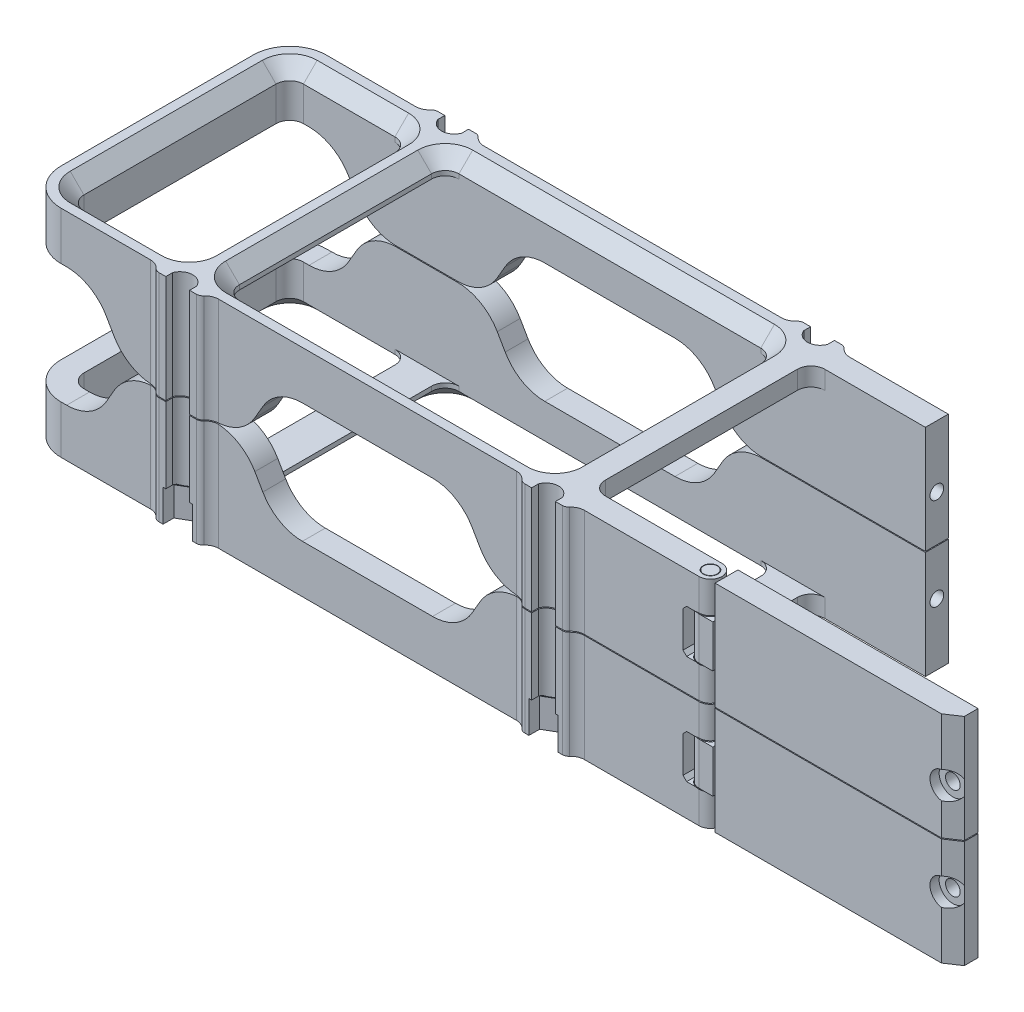
SolidWorks part; units mm, degrees
ref_plane "Płaszczyzna przednia" through (0, 0, 0) normal (0, 0, 1) x (1, 0, 0)
ref_plane "Płaszczyzna górna" through (0, 0, 0) normal (0, 1, 0) x (1, 0, 0)
ref_plane "Płaszczyzna prawa" through (0, 0, 0) normal (1, 0, 0) x (0, 0, -1)
sketch "Szkic1" plane through (0, 0, 0) normal (0, 1, 0) x (1, 0, 0)
  line L0 (-70, -24) -> (75, -24)
  line L1 (75, -24) -> (75, -29)
  line L3 (-75, -29) -> (-75, -24)
  line L4 (75, -29) -> (45.6, -29)
  line L5 (0, 29) -> (0, -29) construction
  line L6 (-34.4, -29) -> (34.4, -29)
  line L7 (-75, -29) -> (-45.6, -29)
  line L8 (-45.6, -29) -> (-40, -29) construction
  line L9 (-40, -29) -> (-34.4, -29) construction
  line L10 (34.4, -29) -> (40, -29) construction
  line L11 (45.6, -29) -> (40, -29) construction
  line L12 (-55, 0) -> (55, 0) construction
  line L13 (45.6, 29) -> (40, 29) construction
  line L14 (34.4, 29) -> (40, 29) construction
  line L15 (-40, 29) -> (-34.4, 29) construction
  line L16 (-45.6, 29) -> (-40, 29) construction
  line L17 (-75, 29) -> (-45.6, 29)
  line L18 (-34.4, 29) -> (34.4, 29)
  line L19 (69, 29) -> (45.6, 29)
  line L20 (-75, 29) -> (-75, 24)
  line L21 (75, 24) -> (75, 29) construction
  line L22 (-70, 24) -> (69, 24)
  line L23 (-75, 24) -> (-75, -24)
  line L24 (-70, 24) -> (-70, -24)
  line L25 (-75, 24) -> (-70, 24) construction
  line L26 (-75, -24) -> (-70, -24) construction
  line L27 (69, 29) -> (69, 24)
  line L28 (69, 24) -> (75, 24) construction
  line L29 (75, 29) -> (69, 29) construction
  arc A0 (-45.6, -29) -> (-34.4, -29) centre (-40, -29) ccw
  arc A1 (34.4, -29) -> (45.6, -29) centre (40, -29) ccw
  arc A2 (-34.4, -29) -> (-45.6, -29) centre (-40, -29) ccw construction
  arc A3 (45.6, -29) -> (34.4, -29) centre (40, -29) ccw construction
  arc A4 (45.6, 29) -> (34.4, 29) centre (40, 29) cw construction
  arc A5 (-34.4, 29) -> (-45.6, 29) centre (-40, 29) cw construction
  arc A6 (34.4, 29) -> (45.6, 29) centre (40, 29) cw
  arc A7 (-45.6, 29) -> (-34.4, 29) centre (-40, 29) cw
  point P4 (0, 0)
  point P12 (0, 0)
  point P16 (0, -29)
  point P31 (0, 29)
  dimension "D1" = 11.2
  dimension "D2" = 11.2
  dimension "D3" = 80
  dimension "D4" = 150
  dimension "D6" = 58
  dimension "D7" = 5
  dimension "D5" = 48
  dimension "D8" = 6
extrude "Dodanie-wyciągnięcie1" add sketch "Szkic1" along normal blind 23.5 separate body
sketch "Szkic2" plane through (0, 23.5, 0) normal (0, 1, 0) x (1, 0, 0)
  line L0 (-45.6, -29) -> (-42.6, -29) construction
  line L3 (-37.4, -29) -> (-34.4, -29) construction
  line L4 (-44.1, -30.5) -> (-42.6, -30.5)
  line L5 (-42.6, -29) -> (-42.6, -30.5)
  line L6 (-37.4, -29) -> (-37.4, -30.5)
  line L7 (-42.6, -30.5) -> (-42.1237, -30.5) construction
  line L8 (-42.1237, -30.5) -> (-37.8763, -30.5) construction
  line L9 (-37.8763, -30.5) -> (-37.4, -30.5) construction
  line L10 (-37.4, -30.5) -> (-35.9, -30.5)
  line L12 (-12.925, 0) -> (12.925, 0) construction
  line L13 (-37.8763, 30.5) -> (-37.4, 30.5) construction
  line L14 (-42.1237, 30.5) -> (-37.8763, 30.5) construction
  line L15 (-42.6, 30.5) -> (-42.1237, 30.5) construction
  line L16 (-37.4, 29) -> (-34.4, 29) construction
  line L22 (-45.6, 29) -> (-42.6, 29) construction
  line L23 (-37.4, 30.5) -> (-35.9, 30.5)
  line L24 (-37.4, 29) -> (-37.4, 30.5)
  line L25 (-42.6, 29) -> (-42.6, 30.5)
  line L26 (-44.1, 30.5) -> (-42.6, 30.5)
  line L27 (0, -12.925) -> (0, 12.925) construction
  line L28 (45.6, 29) -> (42.6, 29) construction
  line L29 (37.4, 29) -> (34.4, 29) construction
  line L30 (42.6, 30.5) -> (42.1237, 30.5) construction
  line L31 (42.1237, 30.5) -> (37.8763, 30.5) construction
  line L40 (37.8763, 30.5) -> (37.4, 30.5) construction
  line L41 (37.8763, -30.5) -> (37.4, -30.5) construction
  line L42 (42.1237, -30.5) -> (37.8763, -30.5) construction
  line L43 (42.6, -30.5) -> (42.1237, -30.5) construction
  line L44 (37.4, -29) -> (34.4, -29) construction
  line L45 (45.6, -29) -> (42.6, -29) construction
  line L46 (44.1, 30.5) -> (42.6, 30.5)
  line L47 (42.6, 29) -> (42.6, 30.5)
  line L48 (37.4, 29) -> (37.4, 30.5)
  line L49 (37.4, 30.5) -> (35.9, 30.5)
  line L50 (37.4, -30.5) -> (35.9, -30.5)
  line L51 (37.4, -29) -> (37.4, -30.5)
  line L52 (42.6, -29) -> (42.6, -30.5)
  line L53 (44.1, -30.5) -> (42.6, -30.5)
  arc A3 (-42.1237, -30.5) -> (-37.8763, -30.5) centre (-40, -29) ccw construction
  arc A4 (-45.6, -29) -> (-44.1, -30.5) centre (-44.1, -29) ccw
  arc A5 (-34.4, -29) -> (-35.9, -30.5) centre (-35.9, -29) cw
  arc A6 (-45.6, -29) -> (-34.4, -29) centre (-40, -29) ccw
  arc A7 (-42.6, -29) -> (-42.1237, -30.5) centre (-40, -29) ccw construction
  arc A8 (-37.8763, -30.5) -> (-37.4, -29) centre (-40, -29) ccw construction
  arc A10 (-37.8763, 30.5) -> (-37.4, 29) centre (-40, 29) cw construction
  arc A11 (-42.6, 29) -> (-42.1237, 30.5) centre (-40, 29) cw construction
  arc A12 (-42.1237, 30.5) -> (-37.8763, 30.5) centre (-40, 29) cw construction
  arc A17 (-42.6, 29) -> (-37.4, 29) centre (-40, 30) ccw
  arc A18 (-45.6, 29) -> (-34.4, 29) centre (-40, 29) cw
  arc A19 (-34.4, 29) -> (-35.9, 30.5) centre (-35.9, 29) ccw
  arc A20 (-45.6, 29) -> (-44.1, 30.5) centre (-44.1, 29) cw
  arc A21 (42.1237, 30.5) -> (37.8763, 30.5) centre (40, 29) ccw construction
  arc A22 (42.6, 29) -> (42.1237, 30.5) centre (40, 29) ccw construction
  arc A31 (-42.6, -29) -> (-37.4, -29) centre (-40, -30) cw
  arc A32 (37.8763, 30.5) -> (37.4, 29) centre (40, 29) ccw construction
  arc A33 (37.8763, -30.5) -> (37.4, -29) centre (40, -29) cw construction
  arc A34 (42.6, -29) -> (42.1237, -30.5) centre (40, -29) cw construction
  arc A35 (42.1237, -30.5) -> (37.8763, -30.5) centre (40, -29) cw construction
  arc A36 (42.6, -29) -> (37.4, -29) centre (40, -30) ccw
  arc A37 (45.6, 29) -> (44.1, 30.5) centre (44.1, 29) ccw
  arc A38 (34.4, 29) -> (35.9, 30.5) centre (35.9, 29) cw
  arc A39 (45.6, 29) -> (34.4, 29) centre (40, 29) ccw
  arc A40 (42.6, 29) -> (37.4, 29) centre (40, 30) cw
  arc A41 (45.6, -29) -> (34.4, -29) centre (40, -29) cw
  arc A42 (34.4, -29) -> (35.9, -30.5) centre (35.9, -29) ccw
  arc A43 (45.6, -29) -> (44.1, -30.5) centre (44.1, -29) cw
  dimension "D1" = 5.2
  dimension "D2" = 1
extrude "Wytnij-wyciągnięcie1" cut sketch "Szkic2" against normal through all
fillet "Zaokrąglenie1" radius 8 2 edges at (-75, 11.75, -29) (-75, 11.75, 29)
fillet "Zaokrąglenie2" radius 3 2 edges at (-70, 11.75, -24) (-70, 11.75, 24)
fillet "Zaokrąglenie3" radius 3 8 edges at (-34.4, 11.75, 29) (-45.6, 11.75, 29) (-45.6, 11.75, -29) (-34.4, 11.75, -29) (34.4, 11.75, -29) (45.6, 11.75, -29) (45.6, 11.75, 29) (34.4, 11.75, 29)
sketch "Szkic6" plane through (0, 23.5, 0) normal (0, 1, 0) x (1, 0, 0)
  line L0 (72.5, -26.5) -> (72.5, -24) construction
  line L1 (75, -24) -> (-67, -24) construction
  line L2 (72.5, -24) -> (75, -24) construction
  circle A0 centre (72.5, -26.5) radius 1.6
  dimension "D3" = 3.2
  dimension "D1" = 2.5
  dimension "D2" = 2.5
extrude "Wytnij-wyciągnięcie4" cut sketch "Szkic6" against normal through all
sketch "Szkic7" plane through (0, 0, 29) normal (0, 0, 1) x (1, 0, 0)
  line L0 (75, 0) -> (75, 7) construction
  line L1 (75, 23.5) -> (75, 0) construction
  line L2 (75, 7) -> (69, 7)
  line L3 (69, 7) -> (69, 16.5)
  line L4 (69, 16.5) -> (75, 16.5)
  line L5 (75, 16.5) -> (75, 7)
  dimension "D1" = 7
  dimension "D2" = 9.5
  dimension "D3" = 6
extrude "Wytnij-wyciągnięcie5" cut sketch "Szkic7" against normal through all
chamfer "Sfazowanie1" distance 1 angle 45 2 edges at (72.5, 16.5, 28.1) (72.5, 7, 24.9)
sketch "Szkic8" plane through (0, 0, 0) normal (0, -1, 0) x (1, 0, 0)
  circle A0 centre (72.5, 26.5) radius 1.5
  dimension "D1" = 3
extrude "Dodanie-wyciągnięcie2" add sketch "Szkic8" against normal blind 23.5 separate body
ref_plane "Płaszczyzna1" through (0, 7.1, 0) normal (0, 1, 0) x (1, 0, 0)
sketch "Szkic9" plane through (0, 7.1, 0) normal (0, 1, 0) x (1, 0, 0)
  circle A0 centre (72.5, -26.5) radius 2.5
  dimension "D1" = 5
extrude "Dodanie-wyciągnięcie3" add sketch "Szkic9" along normal blind 9.3
chamfer "Sfazowanie2" distance 1 angle 45 2 edges at (71, 7.1, 26.5) (71, 16.4, 26.5)
sketch "Szkic10" plane through (0, 0, 0) normal (0, 1, 0) x (1, 0, 0)
  line L0 (0, 0) -> (69.5, 0) construction
  line L1 (69.5, 0) -> (69.5, 29)
  line L2 (69.5, 29) -> (74.5, 29)
  line L3 (74.5, 29) -> (74.5, -23.5)
  line L4 (74.5, -23.5) -> (69.5, -23.5)
  line L5 (69.5, -23.5) -> (69.5, 0)
  dimension "D1" = 69.5
  dimension "D2" = 5
  dimension "D3" = 29
  dimension "D4" = 23.5
extrude "Dodanie-wyciągnięcie4" add sketch "Szkic10" along normal blind 23.5 separate body
sketch "Szkic12" plane through (0, 7.1, 0) normal (0, 1, 0) x (1, 0, 0)
  line L0 (75, -26.5) -> (75, -23.5)
  line L1 (69.5, -23.5) -> (74.5, -23.5) construction
  line L2 (70, -26.5) -> (70, -23.5)
  line L3 (70, -23.5) -> (75, -23.5)
  arc A0 (70, -26.5) -> (75, -26.5) centre (72.5, -26.5) ccw
  arc A1 (75, -26.5) -> (70, -26.5) centre (72.5, -26.5) ccw construction
  dimension "D1" = 5
extrude "Dodanie-wyciągnięcie5" add sketch "Szkic12" along normal blind 9.3
fillet "Zaokrąglenie4" radius 2.5 4 edges at (75, 3.5, 24) (75, 3.5, 29) (75, 20, 29) (75, 20, 24)
ref_axis "Oś1" through (72.5, 25.1302, 26.5) along (0, -1, 0)
sketch "Szkic13" plane through (74.5, 0, 0) normal (1, 0, 0) x (0, 0, -1)
  line L0 (29, 23.5) -> (29, 0) construction
  line L2 (-23.5, 23.5) -> (29, 23.5) construction
  circle A0 centre (26.5, 13.5) radius 1.6
  dimension "D2" = 10
  dimension "D3" = 3.2
  dimension "D1" = 2.5
extrude "Wytnij-wyciągnięcie6" cut sketch "Szkic13" against normal up to next (5 mm away)
sketch "Szkic14" plane through (69, 0, 0) normal (1, 0, 0) x (0, 0, -1)
  circle A0 centre (26.5, 13.5) radius 1.5
  dimension "D1" = 3
extrude "Wytnij-wyciągnięcie7" cut sketch "Szkic14" against normal blind 10
sketch "Szkic15" plane through (74.5, 0, 0) normal (1, 0, 0) x (0, 0, -1)
  circle A0 centre (26.5, 13.5) radius 3
  dimension "D1" = 6
chamfer "Sfazowanie3" distance 3 distance2 2 1 edges at (74.5, 11.75, -29) first distance on face at (74.5, 13.5, -28.1)
extrude "Wytnij-wyciągnięcie8" cut sketch "Szkic15" against normal blind 2
chamfer "Sfazowanie4" distance 0.8 angle 45 2 edges at (69, 16.5, 26.5) (69, 7, 26.5)
move or copy body "Obiekt-Przenieś/Kopiuj1" bodies to move or copy 114 copy no rotation origin (72.5, 0, 26.5) rotation axis (0, -1, 0) rotation angle 90
sketch "Szkic16" plane through (0, 0, 0) normal (0, -1, 0) x (1, 0, 0)
  line L0 (-40, 0) -> (40, 0) construction
  line L1 (40, 24) -> (40, -24) construction
  line L2 (-67, -24) -> (69, -24) construction
  line L4 (72.5, 24) -> (-67, 24) construction
  line L5 (44, 24) -> (44, -24)
  line L6 (44, -24) -> (40, -24)
  line L7 (36, 24) -> (44, 24)
  line L8 (36, 24) -> (36, -24)
  line L9 (36, -24) -> (40, -24)
  line L10 (0, -12.925) -> (0, 12.925) construction
  line L11 (-44, -24) -> (-40, -24)
  line L12 (-36, -24) -> (-40, -24)
  line L13 (-44, 24) -> (-44, -24)
  line L14 (-36, 24) -> (-44, 24)
  line L15 (-36, 24) -> (-36, -24)
  point P4 (0, 0)
  point P10 (40, 0)
  point P17 (40, 24)
  dimension "D1" = 80
  dimension "D2" = 8
extrude "Dodanie-wyciągnięcie6" add sketch "Szkic16" against normal blind 4
sketch "Szkic17" plane through (0, 0, 29) normal (0, 0, 1) x (1, 0, 0)
  line L0 (-75, 10.5) -> (-60, 10.5)
  line L1 (-75, 0) -> (-75, 23.5) construction
  line L2 (-60, 10.5) -> (-52.4944, 23.5)
  line L3 (-67, 23.5) -> (-47.4541, 23.5) construction
  line L4 (-52.4944, 23.5) -> (-75, 23.5)
  line L5 (-75, 23.5) -> (-75, 10.5)
  dimension "D1" = 15
  dimension "D2" = 60
  dimension "D3" = 13
extrude "Wytnij-wyciągnięcie9" cut sketch "Szkic17" against normal through all
sketch "Szkic18" plane through (0, 0, 29) normal (0, 0, 1) x (1, 0, 0)
  line L0 (-27.5056, 23.5) -> (-20, 10.5)
  line L1 (-32.5459, 23.5) -> (32.5459, 23.5) construction
  line L2 (0, 0) -> (0, 10.5) construction
  line L3 (-32.5459, 0) -> (32.5459, 0) construction
  line L4 (20, 10.5) -> (-20, 10.5)
  line L5 (20, 10.5) -> (27.5056, 23.5)
  line L6 (27.5056, 23.5) -> (-27.5056, 23.5)
  point P11 (0, 10.5)
  dimension "D1" = 60
  dimension "D2" = 60
  dimension "D3" = 40
  dimension "D4" = 13
extrude "Wytnij-wyciągnięcie10" cut sketch "Szkic18" against normal through all
fillet "Zaokrąglenie5" radius 10 12 edges at (-52.4944, 23.5, -26.5) (-52.4944, 23.5, 26.5) (-27.5056, 23.5, 26.5) (-20, 10.5, 26.5) (20, 10.5, 26.5) (27.5056, 23.5, 26.5) (-27.5056, 23.5, -26.5) (-20, 10.5, -26.5) (20, 10.5, -26.5) (27.5056, 23.5, -26.5) (-60, 10.5, -26.5) (-60, 10.5, 26.5)
fillet "Zaokrąglenie6" radius 3 8 edges at (-44, 2, -24) (-44, 2, 24) (-36, 2, 24) (-36, 2, -24) (36, 2, -24) (44, 2, -24) (36, 2, 24) (44, 2, 24)
chamfer "Sfazowanie5" distance 3 angle 45 16 edges at (-44, 0, 0) (-44.8787, 0, 23.1213) (-44.8787, 0, -23.1213) (-57, 0, 24) (-57, 0, -24) (-69.1213, 0, 23.1213) (-69.1213, 0, -23.1213) (-70, 0, 0) (36, 0, 0) (35.1213, 0, -23.1213) (35.1213, 0, 23.1213) (0, 0, -24) (0, 0, 24) (-35.1213, 0, -23.1213) (-35.1213, 0, 23.1213) (-36, 0, 0)
ref_plane "Płaszczyzna2" through (0, 23.6, 0) normal (0, 1, 0) x (1, 0, 0)
mirror "Lustro1" about plane through (0, 23.6, 0) normal (0, 1, 0) of bodies 118 111
sketch "Szkic19" plane through (0, 0, 0) normal (0, -1, 0) x (1, 0, 0)
  line L1 (40, -26.305) -> (36.8, -28.1525)
  line L2 (36.8, -28.1525) -> (36.8, -31.8475)
  line L3 (36.8, -31.8475) -> (40, -33.695)
  line L4 (40, -33.695) -> (43.2, -31.8475)
  line L5 (43.2, -31.8475) -> (43.2, -28.1525)
  line L6 (43.2, -28.1525) -> (40, -26.305)
  line L7 (-40, -26.305) -> (-43.2, -28.1525)
  line L8 (-43.2, -28.1525) -> (-43.2, -31.8475)
  line L9 (-43.2, -31.8475) -> (-40, -33.695)
  line L10 (-40, -33.695) -> (-36.8, -31.8475)
  line L11 (-36.8, -31.8475) -> (-36.8, -28.1525)
  line L12 (-36.8, -28.1525) -> (-40, -26.305)
  line L13 (-40, 26.305) -> (-36.8, 28.1525)
  line L14 (-36.8, 28.1525) -> (-36.8, 31.8475)
  line L15 (-36.8, 31.8475) -> (-40, 33.695)
  line L16 (-40, 33.695) -> (-43.2, 31.8475)
  line L17 (-43.2, 31.8475) -> (-43.2, 28.1525)
  line L18 (-43.2, 28.1525) -> (-40, 26.305)
  line L19 (40, 26.305) -> (43.2, 28.1525)
  line L20 (43.2, 28.1525) -> (43.2, 31.8475)
  line L21 (43.2, 31.8475) -> (40, 33.695)
  line L22 (40, 33.695) -> (36.8, 31.8475)
  line L23 (36.8, 31.8475) -> (36.8, 28.1525)
  line L24 (36.8, 28.1525) -> (40, 26.305)
  circle A0 centre (40, -30) radius 3.2 construction
  circle A1 centre (-40, -30) radius 3.2 construction
  circle A2 centre (-40, 30) radius 3.2 construction
  circle A3 centre (40, 30) radius 3.2 construction
  dimension "D1" = 6.4
  dimension "D2" = 6.4
  dimension "D3" = 6.4
  dimension "D4" = 6.4
extrude "Wytnij-wyciągnięcie11" cut sketch "Szkic19" against normal blind 7
chamfer "Sfazowanie6" distance 0.7 angle 45 8 edges at (-38.4, 7, 27.2287) (-41.6, 7, 27.2287) (-41.6, 7, -27.2287) (-38.4, 7, -27.2287) (38.4, 7, -27.2287) (41.6, 7, -27.2287) (41.6, 7, 27.2287) (38.4, 7, 27.2287)
equation "\"Rod_diameter\"= 5.2"
equation "\"D2@Szkic1\"=\"Rod_diameter\"+6"
equation "\"D1@Szkic2\"=\"Rod_diameter\""
equation "\"height\"=23.5"
equation "\"D1@Dodanie-wyciągnięcie1\"=\"height\""
equation "\"D2@Szkic7\"=\"height\"-7*2"
equation "\"D1@Dodanie-wyciągnięcie3\"=\"height\"-2*7-0.2"
equation "\"D1@Dodanie-wyciągnięcie5\"=\"height\"-2*7-0.2"
equation "\"D1@Dodanie-wyciągnięcie2\"=\"height\""
